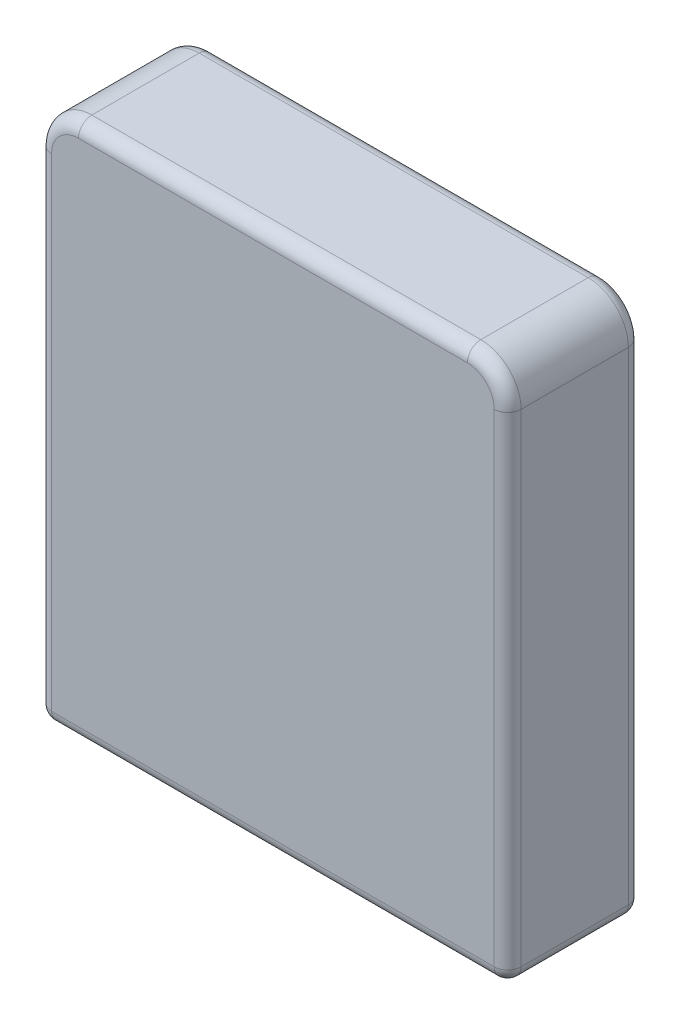
SolidWorks part; units mm, degrees
ref_plane "Front Plane" through (0, 0, 0) normal (0, 0, 1) x (1, 0, 0)
ref_plane "Top Plane" through (0, 0, 0) normal (0, 1, 0) x (1, 0, 0)
ref_plane "Right Plane" through (0, 0, 0) normal (1, 0, 0) x (0, 0, -1)
sketch "Sketch1" plane through (0, 0, 0) normal (0, 0, 1) x (1, 0, 0)
  line L1 (0, 0) -> (35, 0)
  line L2 (0, 0) -> (0, 40)
  line L3 (0, 40) -> (35, 40)
  line L4 (35, 0) -> (35, 40)
  dimension "D1" = 35
  dimension "D2" = 40
extrude "Boss-Extrude1" add sketch "Sketch1" along normal blind 10
fillet "Fillet1" radius 3 2 edges at (0, 40, 5) (35, 40, 5)
sketch "Sketch2" plane through (0, 0, 0) normal (0, -1, 0) x (1, 0, 0)
  line L0 (0, 0) -> (35, 0) construction
  line L1 (5.5, 0) -> (29.5, 0)
  line L2 (5.5, 0) -> (5.5, -2)
  line L3 (5.5, -2) -> (29.5, -2)
  line L4 (29.5, 0) -> (29.5, -2)
  line L5 (0, 10) -> (0, 0) construction
  point P6 (0, 5)
  dimension "D1" = 24
  dimension "D2" = 5.5
  dimension "D3" = 2
extrude "Boss-Extrude2" add sketch "Sketch2" against normal blind 34
fillet "Fillet2" radius 1 6 edges at (5.5, 17, -2) (17.5, 34, -2) (17.5, 34, 0) (29.5, 17, -2)
fillet "Fillet3" radius 1 20 edges at (0, 18.5, 10) (0.8787, 39.1213, 10) (17.5, 40, 10) (34.1213, 39.1213, 10) (0, 18.5, 0) (0.8787, 39.1213, 0) (17.5, 40, 0) (34.1213, 39.1213, 0) (0, 0, 5) (17.5, 0, 10) (35, 0, 5) (29.7929, 0, -0.2929) (29.2071, 0, -1.7071) (17.5, 0, -2) (5.7929, 0, -1.7071) (5.2071, 0, -0.2929) (35, 18.5, 10) (35, 18.5, 0)
